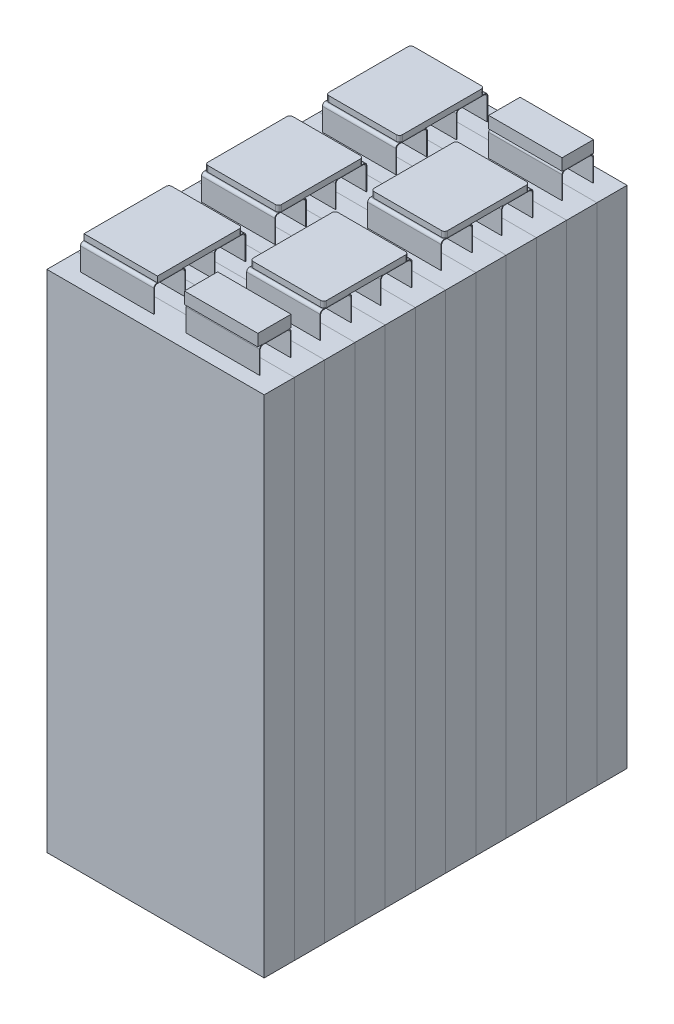
SolidWorks part; units mm, degrees
ref_plane "Front Plane" through (0, 0, 0) normal (0, 0, 1) x (1, 0, 0)
ref_plane "Top Plane" through (0, 0, 0) normal (0, 1, 0) x (1, 0, 0)
ref_plane "Right Plane" through (0, 0, 0) normal (1, 0, 0) x (0, 0, -1)
sketch "Cell Body-S" plane through (0, 0, 0) normal (0, 0, 1) x (1, 0, 0)
  line L0 (-14.8121, 72.7622) -> (10.1879, 72.7622)
  line L1 (-57.3121, 54.7853) -> (16.6879, 54.7853)
  line L2 (-57.3121, 54.7853) -> (-57.3121, -117.2147)
  line L3 (-57.3121, -117.2147) -> (16.6879, -117.2147)
  line L4 (16.6879, 54.7853) -> (16.6879, -117.2147)
  line L5 (-50.8121, 72.7853) -> (-25.8121, 72.7853)
  line L6 (-50.8121, 72.7853) -> (-50.8121, 54.7853)
  line L7 (-50.8121, 54.7853) -> (-25.8121, 54.7853)
  line L8 (-25.8121, 72.7853) -> (-25.8121, 54.7853)
  line L9 (-14.8121, 72.7622) -> (-14.8121, 54.7622)
  line L10 (10.1879, 72.7622) -> (10.1879, 54.7622)
  dimension "D1" = 74
  dimension "D2" = 172
  dimension "D3" = 18
  dimension "D4" = 25
  dimension "D5" = 6.5
  dimension "D6" = 6.5
extrude "Cell Body" add sketch "Cell Body-S" along normal blind 10.3
sketch "Tab-S" plane through (0, 54.7853, 0) normal (0, 1, 0) x (1, 0, 0)
  line L0 (-57.3121, -10.3) -> (-57.3121, 0) construction
  line L1 (-50.8121, -4.95) -> (-25.8121, -4.95)
  line L2 (-50.8121, -4.95) -> (-50.8121, -5.15)
  line L3 (-50.8121, -5.15) -> (-25.8121, -5.15)
  line L4 (-25.8121, -4.95) -> (-25.8121, -5.15)
  line L5 (-57.3121, -10.3) -> (16.6879, -10.3) construction
  line L6 (-14.8121, -4.95) -> (10.1879, -4.95)
  line L7 (-14.8121, -4.95) -> (-14.8121, -5.15)
  line L8 (-14.8121, -5.15) -> (10.1879, -5.15)
  line L9 (10.1879, -4.95) -> (10.1879, -5.15)
  line L10 (16.6879, -10.3) -> (16.6879, 0) construction
  dimension "D1" = 25
  dimension "D2" = 6.5
  dimension "D3" = 0.2
  dimension "D4" = 25
  dimension "D5" = 6.5
  dimension "D6" = 0.2
  dimension "D7" = 5.15
  dimension "D8" = 5.15
extrude "Tab" add sketch "Tab-S" along normal blind 8.5
sketch "Tab Bend-S" plane through (0, 63.2853, 0) normal (0, 1, 0) x (1, 0, 0)
  line L1 (-25.8121, -4.95) -> (-50.8121, -4.95)
  line L2 (-25.8121, -4.95) -> (-25.8121, -14.45)
  line L3 (-25.8121, -14.45) -> (-50.8121, -14.45)
  line L4 (-50.8121, -4.95) -> (-50.8121, -14.45)
  line L5 (10.1879, -4.95) -> (-14.8121, -4.95)
  line L6 (10.1879, -4.95) -> (10.1879, -14.45)
  line L7 (10.1879, -14.45) -> (-14.8121, -14.45)
  line L8 (-14.8121, -4.95) -> (-14.8121, -14.45)
  dimension "D1" = 25
  dimension "D2" = 9.5
  dimension "D3" = 25
  dimension "D4" = 9.5
extrude "Tab Bend" add sketch "Tab Bend-S" along normal blind 0.2
fillet "Tab Fillet" radius 1 4 edges at (-2.3121, 63.2853, 5.15) (-38.3121, 63.2853, 5.15) (-38.3121, 63.4853, 4.95) (-2.3121, 63.4853, 4.95)
mirror "Cell 2" about plane through (0, 0, 10.3) normal (0, 0, 1) of bodies 130
mirror "Cell 3-4" about plane through (0, 0, 20.6) normal (0, 0, -1) of bodies 154 130
mirror "Cell 5-8" about plane through (0, 0, 41.2) normal (0, 0, -1) of bodies 156 155 154 130
mirror "Cell 9-10" about plane through (0, 0, 82.4) normal (0, 0, -1) of bodies 160 159
mirror "Cell 11-12" about plane through (0, 0, 103) normal (0, 0, -1) of bodies 162 161
sketch "Busbars-S" plane through (0, 63.4853, 0) normal (0, 1, 0) x (1, 0, 0)
  line L5 (-49.8121, -6.15) -> (-26.8121, -6.15)
  line L6 (-50.8121, -7.15) -> (-50.8121, -34.05)
  line L7 (-49.8121, -35.05) -> (-26.8121, -35.05)
  line L8 (-25.8121, -7.15) -> (-25.8121, -34.05)
  line L9 (-13.8121, -26.75) -> (9.1879, -26.75)
  line L10 (-14.8121, -27.75) -> (-14.8121, -54.65)
  line L11 (-13.8121, -55.65) -> (9.1879, -55.65)
  line L12 (10.1879, -27.75) -> (10.1879, -54.65)
  line L13 (-49.8121, -47.35) -> (-26.8121, -47.35)
  line L14 (-50.8121, -48.35) -> (-50.8121, -75.25)
  line L15 (-49.8121, -76.25) -> (-26.8121, -76.25)
  line L16 (-25.8121, -48.35) -> (-25.8121, -75.25)
  line L17 (-13.8121, -67.95) -> (9.1879, -67.95)
  line L18 (-14.8121, -68.95) -> (-14.8121, -95.85)
  line L19 (-13.8121, -96.85) -> (9.1879, -96.85)
  line L20 (10.1879, -68.95) -> (10.1879, -95.85)
  line L21 (-49.8121, -88.55) -> (-26.8121, -88.55)
  line L22 (-50.8121, -89.55) -> (-50.8121, -117.45)
  line L23 (-50.8121, -117.45) -> (-25.8121, -117.45)
  line L24 (-25.8121, -89.55) -> (-25.8121, -117.45)
  line L25 (-13.8121, -14.45) -> (9.1879, -14.45)
  line L26 (-14.8121, -13.45) -> (-14.8121, -5.95)
  line L27 (-14.8121, -5.95) -> (10.1879, -5.95)
  line L28 (10.1879, -13.45) -> (10.1879, -5.95)
  line L29 (-13.8121, -109.15) -> (10.1879, -109.15)
  line L30 (-14.8121, -110.15) -> (-14.8121, -116.65)
  line L31 (-13.8121, -117.65) -> (10.1879, -117.65)
  line L32 (10.1879, -109.15) -> (10.1879, -117.65)
  arc A4 (-50.8121, -34.05) -> (-49.8121, -35.05) centre (-49.8121, -34.05) ccw
  arc A5 (-26.8121, -35.05) -> (-25.8121, -34.05) centre (-26.8121, -34.05) ccw
  arc A6 (-26.8121, -6.15) -> (-25.8121, -7.15) centre (-26.8121, -7.15) cw
  arc A7 (-49.8121, -6.15) -> (-50.8121, -7.15) centre (-49.8121, -7.15) ccw
  arc A8 (-14.8121, -54.65) -> (-13.8121, -55.65) centre (-13.8121, -54.65) ccw
  arc A9 (9.1879, -55.65) -> (10.1879, -54.65) centre (9.1879, -54.65) ccw
  arc A10 (9.1879, -26.75) -> (10.1879, -27.75) centre (9.1879, -27.75) cw
  arc A11 (-13.8121, -26.75) -> (-14.8121, -27.75) centre (-13.8121, -27.75) ccw
  arc A12 (-26.8121, -76.25) -> (-25.8121, -75.25) centre (-26.8121, -75.25) ccw
  arc A13 (-50.8121, -75.25) -> (-49.8121, -76.25) centre (-49.8121, -75.25) ccw
  arc A14 (-26.8121, -47.35) -> (-25.8121, -48.35) centre (-26.8121, -48.35) cw
  arc A15 (-49.8121, -47.35) -> (-50.8121, -48.35) centre (-49.8121, -48.35) ccw
  arc A16 (-14.8121, -95.85) -> (-13.8121, -96.85) centre (-13.8121, -95.85) ccw
  arc A17 (9.1879, -96.85) -> (10.1879, -95.85) centre (9.1879, -95.85) ccw
  arc A18 (9.1879, -67.95) -> (10.1879, -68.95) centre (9.1879, -68.95) cw
  arc A19 (-13.8121, -67.95) -> (-14.8121, -68.95) centre (-13.8121, -68.95) ccw
  arc A20 (-26.8121, -88.55) -> (-25.8121, -89.55) centre (-26.8121, -89.55) cw
  arc A21 (-49.8121, -88.55) -> (-50.8121, -89.55) centre (-49.8121, -89.55) ccw
  arc A22 (9.1879, -14.45) -> (10.1879, -13.45) centre (9.1879, -13.45) ccw
  arc A23 (-13.8121, -14.45) -> (-14.8121, -13.45) centre (-13.8121, -13.45) cw
  arc A24 (-14.8121, -116.65) -> (-13.8121, -117.65) centre (-13.8121, -116.65) ccw
  arc A25 (-13.8121, -109.15) -> (-14.8121, -110.15) centre (-13.8121, -110.15) ccw
  point P7 (10.1879, -14.45)
  point P10 (-14.8121, -14.45)
  point P24 (-50.8121, -35.05)
  point P27 (-25.8121, -35.05)
  point P30 (-25.8121, -6.15)
  point P33 (-50.8121, -6.15)
  point P44 (10.1879, -55.65)
  point P49 (-14.8121, -26.75)
  point P58 (-25.8121, -76.25)
  point P65 (-50.8121, -47.35)
  point P76 (10.1879, -96.85)
  point P81 (-14.8121, -67.95)
  point P91 (-50.8121, -88.55)
  point P94 (-14.8121, -109.15)
  dimension "D3" = 8.5
  dimension "D6" = 1
  dimension "D7" = 1
  dimension "D8" = 1
  dimension "D9" = 1
  dimension "D12" = 1
  dimension "D13" = 1
  dimension "D14" = 1
  dimension "D2" = 25
  dimension "D4" = 25
  dimension "D5" = 28.9
  dimension "D10" = 28.9
  dimension "D11" = 25
extrude "Busbars" add sketch "Busbars-S" along normal blind 2 separate body
sketch "Sketch2" plane through (0, 65.4853, 0) normal (0, 1, 0) x (1, 0, 0)
  line L0 (10.1879, -6.15) -> (10.1879, -14.65) construction
  line L1 (-14.8121, -5.95) -> (10.1879, -5.95)
  line L2 (-14.8121, -5.95) -> (-14.8121, -13.45)
  line L3 (-13.8121, -14.45) -> (9.1879, -14.45)
  line L4 (10.1879, -5.95) -> (10.1879, -13.45)
  line L5 (-14.8121, -14.45) -> (10.1879, -14.45) construction
  line L7 (10.1879, -109.15) -> (-13.8121, -109.15)
  line L8 (10.1879, -109.15) -> (10.1879, -117.65)
  line L9 (10.1879, -117.65) -> (-13.8121, -117.65)
  line L10 (-14.8121, -110.15) -> (-14.8121, -116.65)
  arc A0 (9.1879, -14.45) -> (10.1879, -13.45) centre (9.1879, -13.45) ccw
  arc A1 (-14.8121, -13.45) -> (-13.8121, -14.45) centre (-13.8121, -13.45) ccw
  arc A2 (-13.8121, -117.65) -> (-14.8121, -116.65) centre (-13.8121, -116.65) cw
  arc A3 (-13.8121, -109.15) -> (-14.8121, -110.15) centre (-13.8121, -110.15) ccw
  point P11 (10.1879, -14.45)
  point P22 (-14.8121, -117.65)
  dimension "D1" = 1
  dimension "D2" = 1
extrude "Boss-Extrude1" add sketch "Sketch2" along normal blind 2
sketch "Sketch4" plane through (0, 0, 14.45) normal (0, 0, 1) x (1, 0, 0)
  line L0 (-13.8121, 67.4853) -> (-13.8121, 63.4853) construction
  line L1 (-14.8121, 67.4853) -> (10.1879, 67.4853)
  line L2 (-14.8121, 67.4853) -> (-14.8121, 63.4853)
  line L3 (-14.8121, 63.4853) -> (10.1879, 63.4853)
  line L4 (10.1879, 67.4853) -> (10.1879, 63.4853)
  line L5 (-13.8121, 67.4853) -> (9.1879, 67.4853) construction
  dimension "D1" = 25
  dimension "D2" = 24
  dimension "D3" = 4
  dimension "D4" = 4
extrude "Boss-Extrude2" add sketch "Sketch4" along normal blind 1.2 and the other way blind 2
sketch "Sketch5" plane through (0, 0, 5.95) normal (0, 0, -1) x (-1, 0, 0)
  line L1 (-10.1879, 67.4853) -> (14.8121, 67.4853)
  line L2 (-10.1879, 67.4853) -> (-10.1879, 63.4853)
  line L3 (-10.1879, 63.4853) -> (14.8121, 63.4853)
  line L4 (14.8121, 67.4853) -> (14.8121, 63.4853)
extrude "Boss-Extrude3" add sketch "Sketch5" along normal blind 1
sketch "Sketch6" plane through (0, 0, 117.65) normal (0, 0, 1) x (1, 0, 0)
  line L1 (-14.8121, 67.4853) -> (10.1879, 67.4853)
  line L2 (-14.8121, 67.4853) -> (-14.8121, 63.4853)
  line L3 (-14.8121, 63.4853) -> (10.1879, 63.4853)
  line L4 (10.1879, 67.4853) -> (10.1879, 63.4853)
extrude "Boss-Extrude4" add sketch "Sketch6" along normal blind 1.6 and the other way blind 2
sketch "Sketch7" plane through (0, 0, 109.15) normal (0, 0, -1) x (-1, 0, 0)
  line L1 (-10.1879, 67.4853) -> (14.8121, 67.4853)
  line L2 (-10.1879, 67.4853) -> (-10.1879, 63.4853)
  line L3 (-10.1879, 63.4853) -> (14.8121, 63.4853)
  line L4 (14.8121, 67.4853) -> (14.8121, 63.4853)
extrude "Boss-Extrude5" add sketch "Sketch7" along normal blind 1.2 and the other way blind 2
